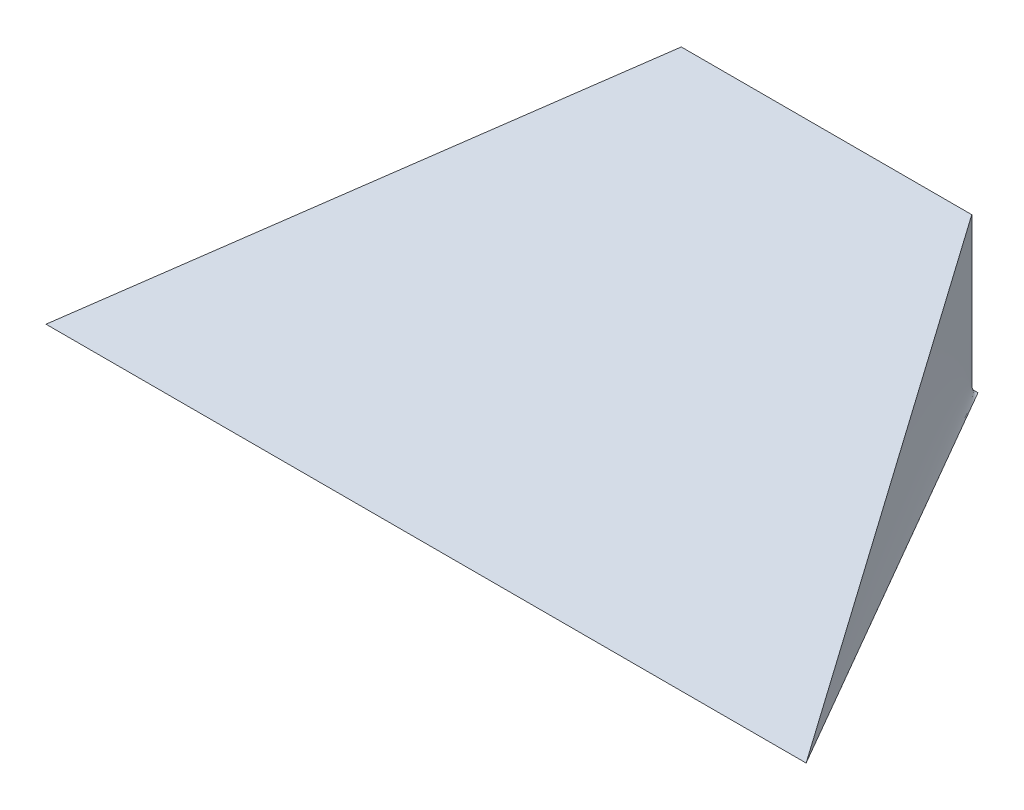
SolidWorks part; units mm, degrees
ref_plane "Plan de face" through (0, 0, 0) normal (0, 0, 1) x (1, 0, 0)
ref_plane "Plan de dessus" through (0, 0, 0) normal (0, 1, 0) x (1, 0, 0)
ref_plane "Plan de droite" through (0, 0, 0) normal (1, 0, 0) x (0, 0, -1)
sketch "Esquisse1" plane through (0, 0, 0) normal (0, 1, 0) x (1, 0, 0)
  line L0 (-38.5189, -7) -> (-34.4774, 0)
  line L3 (-34.4774, 0) -> (-29.4774, 0)
  line L4 (-29.4774, 0) -> (-25.436, -7)
  line L5 (-25.436, -7) -> (-38.5189, -7)
  line L6 (-1.43, 0) -> (1.43, 0) construction
  dimension "D1" = 120
  dimension "D2" = 120
ref_axis "Axe1" through (-34.4774, 0, 0) along (1, 0, 0)
sketch "Esquisse2" plane through (0, 0, 0) normal (0, 0, 1) x (1, 0, 0)
  line L1 (-34.5845, 0) -> (-29.5845, 0)
  line L2 (-34.5845, 0) -> (-34.5845, 2.6)
  line L3 (-34.5845, 2.6) -> (-29.5845, 2.6)
  line L4 (-29.5845, 0) -> (-29.5845, 2.6)
  line L5 (-34.4774, 0) -> (-29.4774, 0) construction
  dimension "D1" = 5
  dimension "D2" = 2.6
loft "Lissage2" add profiles "Esquisse1", "Esquisse2"
